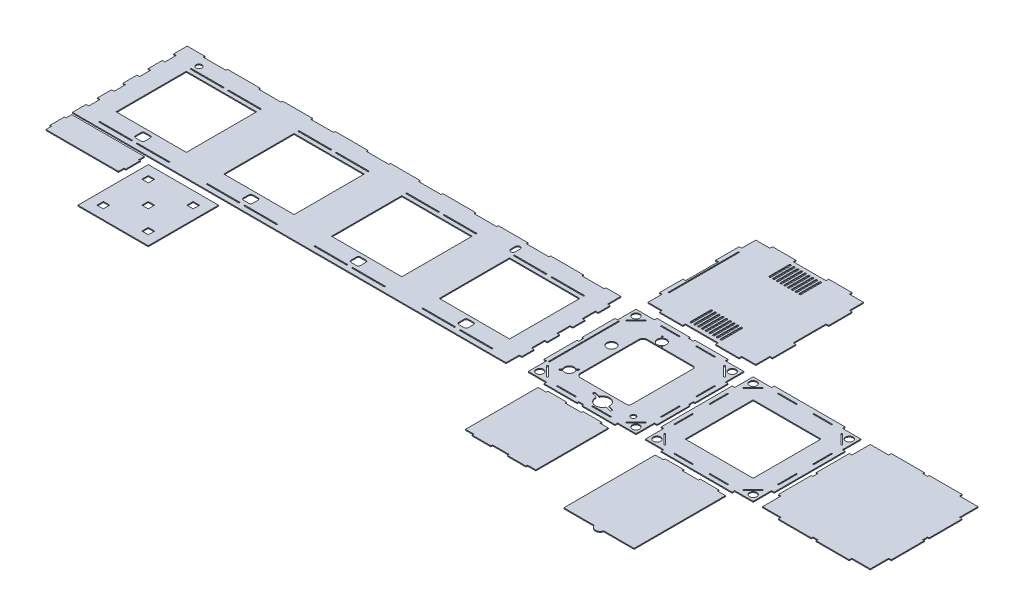
SolidWorks part; units mm, degrees
ref_plane "Front" through (0, 0, 0) normal (0, 0, 1) x (1, 0, 0)
ref_plane "Top" through (0, 0, 0) normal (0, 1, 0) x (1, 0, 0)
ref_plane "Right" through (0, 0, 0) normal (1, 0, 0) x (0, 0, -1)
sketch "Sketch1" plane through (0, 0, 0) normal (0, 1, 0) x (1, 0, 0)
  line L0 (0, 0) -> (438.15, 0) construction
  line L2 (-146.05, 155.575) -> (-146.05, -155.575) construction
  line L4 (146.05, 155.575) -> (146.05, -155.575) construction
  line L5 (-146.05, 155.575) -> (146.05, -155.575) construction
  line L6 (-146.05, -155.575) -> (146.05, 155.575) construction
  line L11 (146.05, 155.575) -> (438.15, 155.575)
  line L12 (146.05, 155.575) -> (146.05, -155.575) construction
  line L13 (146.05, -155.575) -> (438.15, -155.575)
  line L14 (438.15, 155.575) -> (438.15, -155.575) construction
  line L19 (-146.05, -155.575) -> (-438.15, -155.575)
  line L20 (-146.05, -155.575) -> (-146.05, 155.575) construction
  line L21 (-146.05, 155.575) -> (-438.15, 155.575)
  line L28 (146.05, -155.575) -> (-146.05, -155.575)
  line L34 (146.05, 155.575) -> (-146.05, 155.575)
  line L35 (-438.15, 155.575) -> (-438.15, -155.575) construction
  line L43 (-438.15, 155.575) -> (-730.25, 155.575)
  line L44 (-730.25, 155.575) -> (-730.25, -155.575) construction
  line L45 (-730.25, -155.575) -> (-438.15, -155.575)
  line L46 (438.15, 155.575) -> (438.15, 119.6594)
  line L47 (438.15, 119.6594) -> (445.262, 119.6594)
  line L48 (445.262, 119.6594) -> (445.262, 86.7664)
  line L49 (445.262, 86.7664) -> (438.15, 86.7664)
  line L50 (438.15, 86.7664) -> (438.15, 50.8508)
  line L51 (438.15, 50.8508) -> (445.262, 50.8508)
  line L63 (445.262, 50.8508) -> (445.262, 17.9578)
  line L64 (445.262, 17.9578) -> (438.15, 17.9578)
  line L65 (438.15, 17.9578) -> (438.15, -17.9578)
  line L66 (438.15, -17.9578) -> (445.262, -17.9578)
  line L67 (445.262, -17.9578) -> (445.262, -50.8508)
  line L68 (445.262, -50.8508) -> (438.15, -50.8508)
  line L69 (438.15, -50.8508) -> (438.15, -86.7664)
  line L70 (438.15, -86.7664) -> (445.262, -86.7664)
  line L71 (445.262, -86.7664) -> (445.262, -119.6594)
  line L72 (445.262, -119.6594) -> (438.15, -119.6594)
  line L73 (438.15, -119.6594) -> (438.15, -155.575)
  line L74 (-730.25, 155.575) -> (-737.362, 155.575)
  line L76 (-737.362, 118.4529) -> (-730.25, 118.4529)
  line L78 (-730.25, 87.9729) -> (-737.362, 87.9729)
  line L80 (-737.362, 49.6443) -> (-730.25, 49.6443)
  line L82 (-730.25, 19.1643) -> (-737.362, 19.1643)
  line L84 (-737.362, -19.1643) -> (-730.25, -19.1643)
  line L86 (-730.25, -49.6443) -> (-737.362, -49.6443)
  line L88 (-737.362, -87.9729) -> (-730.25, -87.9729)
  line L90 (-730.25, -118.4529) -> (-737.362, -118.4529)
  line L92 (-737.362, -155.575) -> (-730.25, -155.575)
  line L93 (445.262, 34.4043) -> (-730.25, 34.4043) construction
  line L94 (-730.25, 103.2129) -> (445.262, 103.2129) construction
  line L95 (-737.362, 155.575) -> (-737.362, 118.4529)
  line L96 (-737.362, 87.9729) -> (-737.362, 49.6443)
  line L97 (-730.25, 118.4529) -> (-730.25, 87.9729)
  line L98 (-730.25, 49.6443) -> (-730.25, 19.1643)
  line L99 (-730.25, -19.1643) -> (-730.25, -49.6443)
  line L100 (-730.25, -87.9729) -> (-730.25, -118.4529)
  line L101 (-730.25, -103.2129) -> (445.262, -103.2129) construction
  line L102 (-730.25, -34.4043) -> (445.262, -34.4043) construction
  line L103 (-737.362, 19.1643) -> (-737.362, -19.1643)
  line L104 (-737.362, -49.6443) -> (-737.362, -87.9729)
  line L105 (-737.362, -118.4529) -> (-737.362, -155.575)
  point P0 (0, 0)
  dimension "D1" = 292.1
  dimension "D2" = 311.15
  dimension "D3" = 7.112
  dimension "D4" = 32.893
  dimension "D5" = 30.48
extrude "Boss-Extrude1" add sketch "Sketch1" along normal blind 2.54
sketch "Sketch4" plane through (0, 2.54, 0) normal (0, 1, 0) x (1, 0, 0)
  line L0 (-438.15, 155.575) -> (-438.15, -155.575) construction
  line L1 (-438.15, 155.575) -> (-438.15, -155.575)
  line L2 (-146.05, 155.575) -> (-146.05, -155.575) construction
  line L3 (-146.05, 155.575) -> (-146.05, -155.575)
  line L4 (146.05, 155.575) -> (146.05, -155.575) construction
  line L5 (146.05, 155.575) -> (146.05, -155.575)
sketch "Sketch5" plane through (0, 2.54, 0) normal (0, 1, 0) x (1, 0, 0)
  line L0 (-730.25, -19.1643) -> (-730.25, 19.1643) construction
  line L1 (-438.15, 0) -> (-730.25, 0) construction
  line L2 (-438.15, 155.575) -> (-438.15, -155.575) construction
  line L3 (-438.15, 0) -> (-146.05, 0) construction
  line L4 (-146.05, 155.575) -> (-146.05, -155.575) construction
  line L5 (-146.05, 0) -> (146.05, 0) construction
  line L6 (146.05, 155.575) -> (146.05, -155.575) construction
  line L7 (146.05, 0) -> (438.15, 0) construction
  line L8 (438.15, -17.9578) -> (438.15, 17.9578) construction
  line L9 (-584.2, 0) -> (-584.2, -155.575) construction
  line L10 (-737.362, -155.575) -> (438.15, -155.575) construction
  line L11 (-292.1, 0) -> (-292.1, -155.575) construction
  line L12 (0, 0) -> (0, -155.575) construction
  line L13 (292.1, 0) -> (292.1, -155.575) construction
  line L14 (-488.95, -142.875) -> (-488.95, -155.575) construction
  line L15 (-679.45, -139.7508) -> (-488.95, -139.7508)
  line L16 (-679.45, -139.7508) -> (-679.45, -142.875)
  line L17 (-679.45, -142.875) -> (-488.95, -142.875)
  line L18 (-488.95, -139.7508) -> (-488.95, -142.875)
  line L19 (-679.45, -139.7508) -> (-488.95, -142.875) construction
  line L20 (-679.45, -142.875) -> (-488.95, -139.7508) construction
  line L21 (-387.35, -139.7508) -> (-196.85, -139.7508)
  line L22 (-387.35, -139.7508) -> (-387.35, -142.875)
  line L23 (-387.35, -142.875) -> (-196.85, -142.875)
  line L24 (-196.85, -139.7508) -> (-196.85, -142.875)
  line L25 (-387.35, -139.7508) -> (-196.85, -142.875) construction
  line L26 (-387.35, -142.875) -> (-196.85, -139.7508) construction
  line L27 (-95.25, -142.875) -> (95.25, -142.875)
  line L28 (-95.25, -142.875) -> (-95.25, -139.7508)
  line L29 (-95.25, -139.7508) -> (95.25, -139.7508)
  line L30 (95.25, -142.875) -> (95.25, -139.7508)
  line L31 (-95.25, -142.875) -> (95.25, -139.7508) construction
  line L32 (-95.25, -139.7508) -> (95.25, -142.875) construction
  line L33 (196.85, -142.875) -> (387.35, -142.875)
  line L34 (196.85, -142.875) -> (196.85, -139.7508)
  line L35 (196.85, -139.7508) -> (387.35, -139.7508)
  line L36 (387.35, -142.875) -> (387.35, -139.7508)
  line L37 (196.85, -142.875) -> (387.35, -139.7508) construction
  line L38 (196.85, -139.7508) -> (387.35, -142.875) construction
  line L39 (196.85, 139.7508) -> (387.35, 142.875) construction
  line L40 (196.85, 142.875) -> (387.35, 139.7508) construction
  line L41 (-95.25, 139.7508) -> (95.25, 142.875) construction
  line L42 (-95.25, 142.875) -> (95.25, 139.7508) construction
  line L43 (-387.35, 142.875) -> (-196.85, 139.7508) construction
  line L44 (-387.35, 139.7508) -> (-196.85, 142.875) construction
  line L45 (-679.45, 142.875) -> (-488.95, 139.7508) construction
  line L46 (-679.45, 139.7508) -> (-488.95, 142.875) construction
  line L47 (-584.2, 0) -> (-584.2, 106.9721) construction
  line L48 (387.35, 142.875) -> (387.35, 139.7508) construction
  line L49 (196.85, 139.7508) -> (387.35, 139.7508) construction
  line L50 (196.85, 142.875) -> (196.85, 139.7508) construction
  line L51 (196.85, 142.875) -> (387.35, 142.875) construction
  line L52 (95.25, 142.875) -> (95.25, 139.7508) construction
  line L53 (-95.25, 139.7508) -> (95.25, 139.7508) construction
  line L54 (-95.25, 142.875) -> (-95.25, 139.7508) construction
  line L55 (-95.25, 142.875) -> (95.25, 142.875) construction
  line L56 (-196.85, 139.7508) -> (-196.85, 142.875) construction
  line L57 (-387.35, 142.875) -> (-196.85, 142.875) construction
  line L58 (-387.35, 139.7508) -> (-387.35, 142.875) construction
  line L59 (-387.35, 139.7508) -> (-196.85, 139.7508) construction
  line L60 (-488.95, 139.7508) -> (-488.95, 142.875) construction
  line L61 (-679.45, 142.875) -> (-488.95, 142.875) construction
  line L62 (-679.45, 139.7508) -> (-679.45, 142.875) construction
  line L63 (-679.45, 139.7508) -> (-488.95, 139.7508) construction
  line L64 (-292.1, 0) -> (-292.1, 106.9721) construction
  line L65 (-679.45, 95.25) -> (-488.95, 95.25)
  line L66 (-679.45, 95.25) -> (-679.45, -95.25)
  line L67 (-679.45, -95.25) -> (-488.95, -95.25)
  line L68 (-488.95, 95.25) -> (-488.95, -95.25)
  line L69 (-679.45, 95.25) -> (-488.95, -95.25) construction
  line L70 (-679.45, -95.25) -> (-488.95, 95.25) construction
  line L71 (-387.35, 95.25) -> (-196.85, 95.25)
  line L72 (-387.35, 95.25) -> (-387.35, -95.25)
  line L73 (-387.35, -95.25) -> (-196.85, -95.25)
  line L74 (-196.85, 95.25) -> (-196.85, -95.25)
  line L75 (-387.35, 95.25) -> (-196.85, -95.25) construction
  line L76 (-387.35, -95.25) -> (-196.85, 95.25) construction
  line L77 (-95.25, 95.25) -> (95.25, 95.25)
  line L78 (-95.25, 95.25) -> (-95.25, -95.25)
  line L79 (-95.25, -95.25) -> (95.25, -95.25)
  line L80 (95.25, 95.25) -> (95.25, -95.25)
  line L81 (-95.25, 95.25) -> (95.25, -95.25) construction
  line L82 (-95.25, -95.25) -> (95.25, 95.25) construction
  line L83 (196.85, 95.25) -> (387.35, 95.25)
  line L84 (196.85, 95.25) -> (196.85, -95.25)
  line L85 (196.85, -95.25) -> (387.35, -95.25)
  line L86 (387.35, 95.25) -> (387.35, -95.25)
  line L87 (196.85, 95.25) -> (387.35, -95.25) construction
  line L88 (196.85, -95.25) -> (387.35, 95.25) construction
  line L89 (0, 0) -> (0, 106.9721) construction
  line L90 (292.1, 0) -> (292.1, 106.9721) construction
  line L91 (-387.35, -95.25) -> (-387.35, -139.7508) construction
  line L92 (-679.45, 108.5342) -> (-488.95, 108.5342)
  line L93 (-679.45, 108.5342) -> (-679.45, 105.41)
  line L94 (-679.45, 105.41) -> (-488.95, 105.41)
  line L95 (-488.95, 108.5342) -> (-488.95, 105.41)
  line L96 (-679.45, 108.5342) -> (-488.95, 105.41) construction
  line L97 (-679.45, 105.41) -> (-488.95, 108.5342) construction
  line L98 (-387.35, 108.5342) -> (-196.85, 108.5342)
  line L99 (-387.35, 108.5342) -> (-387.35, 105.41)
  line L100 (-387.35, 105.41) -> (-196.85, 105.41)
  line L101 (-196.85, 108.5342) -> (-196.85, 105.41)
  line L102 (-387.35, 108.5342) -> (-196.85, 105.41) construction
  line L103 (-387.35, 105.41) -> (-196.85, 108.5342) construction
  line L104 (-95.25, 108.5342) -> (95.25, 108.5342)
  line L105 (-95.25, 108.5342) -> (-95.25, 105.41)
  line L106 (-95.25, 105.41) -> (95.25, 105.41)
  line L107 (95.25, 108.5342) -> (95.25, 105.41)
  line L108 (-95.25, 108.5342) -> (95.25, 105.41) construction
  line L109 (-95.25, 105.41) -> (95.25, 108.5342) construction
  line L110 (196.85, 108.5342) -> (387.35, 108.5342)
  line L111 (196.85, 108.5342) -> (196.85, 105.41)
  line L112 (196.85, 105.41) -> (387.35, 105.41)
  line L113 (387.35, 108.5342) -> (387.35, 105.41)
  line L114 (196.85, 108.5342) -> (387.35, 105.41) construction
  line L115 (196.85, 105.41) -> (387.35, 108.5342) construction
  line L116 (-196.85, -95.25) -> (-196.85, -139.7508) construction
  line L117 (-196.85, -117.5004) -> (-387.35, -117.5004) construction
  line L118 (-7.62, -130.2258) -> (7.62, -130.2258)
  line L119 (-299.72, -104.775) -> (-284.48, -104.775)
  line L120 (-304.8, -109.855) -> (-304.8, -125.1458)
  line L121 (-299.72, -130.2258) -> (-284.48, -130.2258)
  line L122 (-279.4, -109.855) -> (-279.4, -125.1458)
  line L123 (-304.8, -104.775) -> (-279.4, -130.2258) construction
  line L124 (-304.8, -130.2258) -> (-279.4, -104.775) construction
  line L125 (-12.7, -109.855) -> (-12.7, -125.1458)
  line L126 (-7.62, -104.775) -> (7.62, -104.775)
  line L127 (12.7, -109.855) -> (12.7, -125.1458)
  line L128 (284.48, -130.2258) -> (299.72, -130.2258)
  line L129 (279.4, -109.855) -> (279.4, -125.1458)
  line L130 (284.48, -104.775) -> (299.72, -104.775)
  line L131 (304.8, -109.855) -> (304.8, -125.1458)
  line L132 (-596.9, -109.855) -> (-596.9, -125.1458)
  line L133 (-591.82, -104.775) -> (-576.58, -104.775)
  line L134 (-571.5, -109.855) -> (-571.5, -125.1458)
  line L135 (-591.82, -130.2258) -> (-576.58, -130.2258)
  line L136 (438.15, 155.575) -> (-737.362, 155.575) construction
  line L137 (184.15, 130.1242) -> (184.15, 117.4242) construction
  line L138 (190.5, 130.1242) -> (190.5, 117.4242)
  line L139 (177.8, 130.1242) -> (177.8, 117.4242)
  line L141 (-737.362, 155.575) -> (-737.362, 118.4529) construction
  line L142 (184.15, 123.7742) -> (-673.862, 123.7742) construction
  arc A0 (-284.48, -104.775) -> (-279.4, -109.855) centre (-284.48, -109.855) cw
  arc A1 (-279.4, -125.1458) -> (-284.48, -130.2258) centre (-284.48, -125.1458) cw
  arc A2 (-299.72, -130.2258) -> (-304.8, -125.1458) centre (-299.72, -125.1458) cw
  arc A3 (-304.8, -109.855) -> (-299.72, -104.775) centre (-299.72, -109.855) cw
  arc A4 (-7.62, -130.2258) -> (-12.7, -125.1458) centre (-7.62, -125.1458) cw
  arc A5 (-12.7, -109.855) -> (-7.62, -104.775) centre (-7.62, -109.855) cw
  arc A6 (7.62, -104.775) -> (12.7, -109.855) centre (7.62, -109.855) cw
  arc A7 (12.7, -125.1458) -> (7.62, -130.2258) centre (7.62, -125.1458) cw
  arc A8 (284.48, -130.2258) -> (279.4, -125.1458) centre (284.48, -125.1458) cw
  arc A9 (279.4, -109.855) -> (284.48, -104.775) centre (284.48, -109.855) cw
  arc A10 (299.72, -104.775) -> (304.8, -109.855) centre (299.72, -109.855) cw
  arc A11 (304.8, -125.1458) -> (299.72, -130.2258) centre (299.72, -125.1458) cw
  arc A12 (-596.9, -109.855) -> (-591.82, -104.775) centre (-591.82, -109.855) cw
  arc A13 (-591.82, -130.2258) -> (-596.9, -125.1458) centre (-591.82, -125.1458) cw
  arc A14 (-576.58, -104.775) -> (-571.5, -109.855) centre (-576.58, -109.855) cw
  arc A15 (-571.5, -125.1458) -> (-576.58, -130.2258) centre (-576.58, -125.1458) cw
  arc A16 (190.5, 130.1242) -> (177.8, 130.1242) centre (184.15, 130.1242) ccw
  arc A17 (177.8, 117.4242) -> (190.5, 117.4242) centre (184.15, 117.4242) ccw
  circle A18 centre (-673.862, 123.7742) radius 7.9375
  point P27 (-584.2, -141.3129)
  point P32 (-292.1, -141.3129)
  point P37 (0, -141.3129)
  point P42 (292.1, -141.3129)
  point P66 (292.1, 141.3129)
  point P67 (0, 141.3129)
  point P68 (-292.1, 141.3129)
  point P69 (-584.2, 141.3129)
  point P106 (-292.1, -117.5004)
  point P148 (0, -130.2258)
  point P161 (-584.2, -130.2258)
  point P165 (184.15, 123.7742)
  dimension "D5" = 10.16
  dimension "D7" = 9.525
  dimension "D9" = 5.08
  dimension "D14" = 25.4
  dimension "D16" = 2.54
  dimension "D17" = 15.875
  dimension "D18" = 63.5
  dimension "D1" = 12.7
  dimension "D2" = 3.1242
  dimension "D3" = 190.5
  dimension "D4" = 190.5
  dimension "D6" = 9.525
  dimension "D8" = 25.4
  dimension "D10" = 3
  dimension "D12" = 47.0408
  dimension "D13" = 12.7
  dimension "D15" = 38.1
  dimension "D11" = 2
extrude "Cut-Extrude2" cut sketch "Sketch5" against normal through all
sketch "Sketch6" plane through (0, 0, 0) normal (0, 1, 0) x (1, 0, 0)
  line L0 (0, 0) -> (635, 0) construction
  line L1 (635, 0) -> (635, 149.606) construction
  line L2 (488.95, 146.05) -> (781.05, 146.05) construction
  line L3 (488.95, 146.05) -> (488.95, -146.05) construction
  line L4 (488.95, -146.05) -> (781.05, -146.05) construction
  line L5 (781.05, 146.05) -> (781.05, -146.05) construction
  line L6 (488.95, 146.05) -> (781.05, -146.05) construction
  line L7 (488.95, -146.05) -> (781.05, 146.05) construction
  line L8 (635, 0) -> (784.606, 0) construction
  line L9 (635, 0) -> (635, -149.606) construction
  line L10 (488.95, 96.139) -> (488.95, 146.05)
  line L11 (538.861, 153.162) -> (731.139, 153.162)
  line L12 (538.861, 153.162) -> (538.861, 146.05)
  line L13 (538.861, 146.05) -> (731.139, 146.05) construction
  line L14 (731.139, 153.162) -> (731.139, 146.05)
  line L15 (538.861, 153.162) -> (731.139, 146.05) construction
  line L16 (538.861, 146.05) -> (731.139, 153.162) construction
  line L17 (788.162, -96.139) -> (781.05, -96.139)
  line L18 (788.162, -96.139) -> (788.162, 96.139)
  line L19 (788.162, 96.139) -> (781.05, 96.139)
  line L20 (781.05, -96.139) -> (781.05, 96.139) construction
  line L21 (788.162, -96.139) -> (781.05, 96.139) construction
  line L22 (788.162, 96.139) -> (781.05, -96.139) construction
  line L23 (538.861, -153.162) -> (731.139, -153.162)
  line L24 (538.861, -153.162) -> (538.861, -146.05)
  line L25 (538.861, -146.05) -> (731.139, -146.05) construction
  line L26 (731.139, -153.162) -> (731.139, -146.05)
  line L27 (538.861, -153.162) -> (731.139, -146.05) construction
  line L28 (538.861, -146.05) -> (731.139, -153.162) construction
  line L29 (481.838, 96.139) -> (488.95, 96.139)
  line L30 (481.838, 96.139) -> (481.838, -96.139)
  line L31 (481.838, -96.139) -> (488.95, -96.139)
  line L32 (488.95, 96.139) -> (488.95, -96.139) construction
  line L33 (481.838, 96.139) -> (488.95, -96.139) construction
  line L34 (481.838, -96.139) -> (488.95, 96.139) construction
  line L35 (488.95, 146.05) -> (538.861, 146.05)
  line L36 (731.139, 146.05) -> (781.05, 146.05)
  line L37 (781.05, 146.05) -> (781.05, 96.139)
  line L38 (781.05, -96.139) -> (781.05, -146.05)
  line L39 (781.05, -146.05) -> (731.139, -146.05)
  line L40 (538.861, -146.05) -> (488.95, -146.05)
  line L41 (488.95, -146.05) -> (488.95, -96.139)
  line L42 (799.338, 96.139) -> (799.338, -96.139)
  line L43 (799.338, 96.139) -> (806.45, 96.139)
  line L44 (806.45, 96.139) -> (806.45, 146.05)
  line L45 (806.45, 146.05) -> (856.361, 146.05)
  line L46 (856.361, 153.162) -> (856.361, 146.05)
  line L47 (856.361, 153.162) -> (1048.639, 153.162)
  line L48 (1048.639, 153.162) -> (1048.639, 146.05)
  line L49 (1048.639, 146.05) -> (1098.55, 146.05)
  line L50 (1098.55, 146.05) -> (1098.55, 96.139)
  line L51 (1105.662, 96.139) -> (1098.55, 96.139)
  line L52 (1105.662, -96.139) -> (1105.662, 96.139)
  line L53 (1105.662, -96.139) -> (1098.55, -96.139)
  line L54 (1098.55, -96.139) -> (1098.55, -146.05)
  line L55 (1098.55, -146.05) -> (1048.639, -146.05)
  line L56 (1048.639, -153.162) -> (1048.639, -146.05)
  line L57 (856.361, -153.162) -> (1048.639, -153.162)
  line L58 (856.361, -153.162) -> (856.361, -146.05)
  line L59 (856.361, -146.05) -> (806.45, -146.05)
  line L60 (806.45, -146.05) -> (806.45, -96.139)
  line L61 (799.338, -96.139) -> (806.45, -96.139)
  line L62 (806.45, 146.05) -> (1098.55, -146.05) construction
  line L63 (1116.838, 96.139) -> (1116.838, -96.139)
  line L64 (1116.838, 96.139) -> (1123.95, 96.139)
  line L65 (1123.95, 96.139) -> (1123.95, 146.05)
  line L66 (1123.95, 146.05) -> (1173.861, 146.05)
  line L67 (1173.861, 153.162) -> (1173.861, 146.05)
  line L68 (1173.861, 153.162) -> (1366.139, 153.162)
  line L69 (1366.139, 153.162) -> (1366.139, 146.05)
  line L70 (1366.139, 146.05) -> (1416.05, 146.05)
  line L71 (1416.05, 146.05) -> (1416.05, 96.139)
  line L72 (1423.162, 96.139) -> (1416.05, 96.139)
  line L73 (1423.162, -96.139) -> (1423.162, 96.139)
  line L74 (1423.162, -96.139) -> (1416.05, -96.139)
  line L75 (1416.05, -96.139) -> (1416.05, -146.05)
  line L76 (1416.05, -146.05) -> (1366.139, -146.05)
  line L77 (1366.139, -153.162) -> (1366.139, -146.05)
  line L78 (1173.861, -153.162) -> (1366.139, -153.162)
  line L79 (1173.861, -153.162) -> (1173.861, -146.05)
  line L80 (1173.861, -146.05) -> (1123.95, -146.05)
  line L81 (1123.95, -146.05) -> (1123.95, -96.139)
  line L82 (1116.838, -96.139) -> (1123.95, -96.139)
  line L83 (1270, 153.162) -> (1270, -153.162) construction
  line L84 (860.425, 92.075) -> (1044.575, 92.075)
  line L85 (860.425, 92.075) -> (860.425, -92.075)
  line L86 (860.425, -92.075) -> (1044.575, -92.075)
  line L87 (1044.575, 92.075) -> (1044.575, -92.075)
  line L88 (860.425, 92.075) -> (1044.575, -92.075) construction
  line L89 (860.425, -92.075) -> (1044.575, 92.075) construction
  point P22 (485.394, 0)
  point P67 (952.5, 0)
  dimension "D1" = 292.1
  dimension "D2" = 292.1
  dimension "D3" = 7.112
  dimension "D4" = 192.278
  dimension "D5" = 635
  dimension "D7" = 317.5
  dimension "D8" = 184.15
  dimension "D9" = 11.176
  dimension "D6" = 3
extrude "Boss-Extrude2" add sketch "Sketch6" along normal blind 2.54 separate body
sketch "Sketch7" plane through (0, 0, 0) normal (0, 1, 0) x (1, 0, 0)
  line L0 (-679.45, 105.41) -> (-679.45, -91.186) construction
  line L1 (-732.917, -161.925) -> (-536.321, -161.925)
  line L2 (-732.917, -161.925) -> (-732.917, -177.165)
  line L3 (-732.917, -231.775) -> (-536.321, -231.775)
  line L4 (-536.321, -161.925) -> (-536.321, -177.165)
  line L5 (-732.917, -161.925) -> (-536.321, -231.775) construction
  line L6 (-732.917, -231.775) -> (-536.321, -161.925) construction
  line L7 (-679.45, 95.25) -> (-679.45, -95.25) construction
  line L8 (-679.45, -91.186) -> (-679.45, -95.25) construction
  line L9 (488.95, -96.139) -> (488.95, -146.05) construction
  line L10 (488.95, -146.05) -> (538.861, -146.05) construction
  line L12 (-732.917, -177.165) -> (-737.362, -177.165)
  line L13 (502.6443, -105.415) -> (529.585, -132.3557) construction
  line L14 (502.6443, -105.415) -> (500.4351, -107.6241) construction
  line L15 (500.4351, -107.6241) -> (527.3759, -134.5649) construction
  line L16 (529.585, -132.3557) -> (527.3759, -134.5649) construction
  line L17 (502.6443, -105.415) -> (527.3759, -134.5649) construction
  line L18 (500.4351, -107.6241) -> (529.585, -132.3557) construction
  line L19 (-737.362, -177.165) -> (-737.362, -216.535)
  line L20 (-737.362, -216.535) -> (-732.917, -216.535)
  line L21 (488.95, -96.139) -> (538.861, -146.05) construction
  line L22 (515.0101, -119.9899) -> (513.9055, -121.0945) construction
  line L23 (-732.917, -216.535) -> (-732.917, -231.775)
  line L24 (-536.321, -177.165) -> (-531.876, -177.165)
  line L25 (-531.876, -177.165) -> (-531.876, -216.535)
  line L26 (-531.876, -216.535) -> (-536.321, -216.535)
  line L27 (-536.321, -216.535) -> (-536.321, -231.775)
  line L28 (-737.362, -155.575) -> (438.15, -155.575) construction
  line L29 (-737.362, -118.4529) -> (-737.362, -155.575) construction
  point P0 (-634.619, -196.85)
  point P14 (515.0101, -119.9899)
  dimension "D1" = 69.85
  dimension "D2" = 4.064
  dimension "D3" = 3.1242
  dimension "D4" = 39.37
  dimension "D5" = 38.1
  dimension "D6" = 4.445
  dimension "D7" = 6.35
extrude "Boss-Extrude3" add sketch "Sketch7" along normal blind 2.54 separate body
sketch "Sketch8" plane through (0, 2.54, 0) normal (0, 1, 0) x (1, 0, 0)
  line L0 (500.4351, -107.6241) -> (527.3759, -134.5649) construction
  line L1 (529.585, -132.3557) -> (527.3759, -134.5649) construction
  line L2 (502.6443, -105.415) -> (529.585, -132.3557) construction
  line L3 (502.6443, -105.415) -> (500.4351, -107.6241) construction
  line L4 (500.4351, -107.6241) -> (527.3759, -134.5649)
  line L5 (529.585, -132.3557) -> (527.3759, -134.5649)
  line L6 (502.6443, -105.415) -> (529.585, -132.3557)
  line L7 (502.6443, -105.415) -> (500.4351, -107.6241)
  line L8 (488.95, 146.05) -> (781.05, -146.05) construction
  line L9 (529.585, 132.3557) -> (502.6443, 105.415)
  line L10 (529.585, 132.3557) -> (527.3759, 134.5649)
  line L11 (527.3759, 134.5649) -> (500.4351, 107.6241)
  line L12 (502.6443, 105.415) -> (500.4351, 107.6241)
  line L13 (767.3557, 105.415) -> (740.415, 132.3557)
  line L14 (767.3557, 105.415) -> (769.5649, 107.6241)
  line L15 (769.5649, 107.6241) -> (742.6241, 134.5649)
  line L16 (740.415, 132.3557) -> (742.6241, 134.5649)
  line L17 (740.415, -132.3557) -> (767.3557, -105.415)
  line L18 (740.415, -132.3557) -> (742.6241, -134.5649)
  line L19 (742.6241, -134.5649) -> (769.5649, -107.6241)
  line L20 (767.3557, -105.415) -> (769.5649, -107.6241)
  line L21 (806.45, -96.139) -> (856.361, -146.05) construction
  line L22 (817.9351, -107.6241) -> (820.1443, -105.415)
  line L23 (820.1443, -105.415) -> (847.085, -132.3557)
  line L24 (847.085, -132.3557) -> (844.8759, -134.5649)
  line L25 (831.4055, -121.0945) -> (833.6146, -118.8854) construction
  line L26 (817.9351, -107.6241) -> (844.8759, -134.5649)
  line L27 (806.45, 146.05) -> (1098.55, -146.05) construction
  line L28 (820.1443, 105.415) -> (817.9351, 107.6241)
  line L29 (844.8759, 134.5649) -> (817.9351, 107.6241)
  line L30 (844.8759, 134.5649) -> (847.085, 132.3557)
  line L31 (847.085, 132.3557) -> (820.1443, 105.415)
  line L32 (1057.915, 132.3557) -> (1060.1241, 134.5649)
  line L33 (1087.0649, 107.6241) -> (1060.1241, 134.5649)
  line L34 (1087.0649, 107.6241) -> (1084.8557, 105.415)
  line L35 (1084.8557, 105.415) -> (1057.915, 132.3557)
  line L36 (1084.8557, -105.415) -> (1087.0649, -107.6241)
  line L37 (1060.1241, -134.5649) -> (1087.0649, -107.6241)
  line L38 (1060.1241, -134.5649) -> (1057.915, -132.3557)
  line L39 (1057.915, -132.3557) -> (1084.8557, -105.415)
  circle A0 centre (635, 0) radius 20.7898 construction
  circle A1 centre (635, 0) radius 20.7898 construction
  circle A2 centre (635, 0) radius 20.7898 construction
  circle A3 centre (635, 0) radius 20.7898 construction
  circle A4 centre (952.5, 0) radius 130.2137 construction
  circle A5 centre (822.1654, 130.3346) radius 10
  circle A9 centre (1082.8346, 130.3346) radius 10
  circle A10 centre (1082.8346, -130.3346) radius 10
  circle A11 centre (822.1654, -130.3346) radius 10
  circle A12 centre (504.6654, 130.3346) radius 10
  circle A13 centre (765.3346, 130.3346) radius 10
  circle A14 centre (765.3346, -130.3346) radius 10
  circle A15 centre (504.6654, -130.3346) radius 10
  point P28 (635, 0)
  point P58 (952.5, 0)
  point P67 (952.5, 0)
  point P76 (635, 0)
  dimension "D3" = 20
  dimension "D4" = 22.225
  dimension "D6" = 22.225
  dimension "D1" = 4
  dimension "D2" = 4
  dimension "D5" = 4
  dimension "D7" = 4
extrude "Cut-Extrude3" cut sketch "Sketch8" against normal through all
sketch "Sketch9" plane through (0, 0, 0) normal (0, 1, 0) x (1, 0, 0)
  line L0 (-737.362, -155.575) -> (438.15, -155.575) construction
  line L1 (-511.876, -175.575) -> (-321.376, -175.575)
  line L2 (-511.876, -175.575) -> (-511.876, -366.075)
  line L3 (-511.876, -366.075) -> (-321.376, -366.075)
  line L4 (-321.376, -175.575) -> (-321.376, -366.075)
  line L5 (-511.876, -175.575) -> (-321.376, -366.075) construction
  line L6 (-511.876, -366.075) -> (-321.376, -175.575) construction
  line L7 (-425.262, -262.189) -> (-407.99, -262.189)
  line L8 (-425.262, -262.189) -> (-425.262, -279.461)
  line L9 (-425.262, -279.461) -> (-407.99, -279.461)
  line L10 (-407.99, -262.189) -> (-407.99, -279.461)
  line L11 (-425.262, -262.189) -> (-407.99, -279.461) construction
  line L12 (-425.262, -279.461) -> (-407.99, -262.189) construction
  line L13 (-477.5247, -209.9263) -> (-355.7273, -209.9263) construction
  line L14 (-477.5247, -209.9263) -> (-477.5247, -331.7237) construction
  line L15 (-477.5247, -331.7237) -> (-355.7273, -331.7237) construction
  line L16 (-355.7273, -209.9263) -> (-355.7273, -331.7237) construction
  line L17 (-477.5247, -209.9263) -> (-355.7273, -331.7237) construction
  line L18 (-477.5247, -331.7237) -> (-355.7273, -209.9263) construction
  line L19 (-486.1607, -201.2903) -> (-468.8887, -201.2903)
  line L20 (-486.1607, -201.2903) -> (-486.1607, -218.5623)
  line L21 (-486.1607, -218.5623) -> (-468.8887, -218.5623)
  line L22 (-468.8887, -201.2903) -> (-468.8887, -218.5623)
  line L23 (-486.1607, -201.2903) -> (-468.8887, -218.5623) construction
  line L24 (-486.1607, -218.5623) -> (-468.8887, -201.2903) construction
  line L25 (-486.1607, -323.0877) -> (-468.8887, -323.0877)
  line L26 (-486.1607, -323.0877) -> (-486.1607, -340.3597)
  line L27 (-486.1607, -340.3597) -> (-468.8887, -340.3597)
  line L28 (-468.8887, -323.0877) -> (-468.8887, -340.3597)
  line L29 (-486.1607, -323.0877) -> (-468.8887, -340.3597) construction
  line L30 (-486.1607, -340.3597) -> (-468.8887, -323.0877) construction
  line L31 (-347.0913, -323.0877) -> (-364.3633, -323.0877)
  line L32 (-347.0913, -323.0877) -> (-347.0913, -340.3597)
  line L33 (-347.0913, -340.3597) -> (-364.3633, -340.3597)
  line L34 (-364.3633, -323.0877) -> (-364.3633, -340.3597)
  line L35 (-347.0913, -323.0877) -> (-364.3633, -340.3597) construction
  line L36 (-347.0913, -340.3597) -> (-364.3633, -323.0877) construction
  line L37 (-364.3633, -201.2903) -> (-347.0913, -201.2903)
  line L38 (-364.3633, -201.2903) -> (-364.3633, -218.5623)
  line L39 (-364.3633, -218.5623) -> (-347.0913, -218.5623)
  line L40 (-347.0913, -201.2903) -> (-347.0913, -218.5623)
  line L41 (-364.3633, -201.2903) -> (-347.0913, -218.5623) construction
  line L42 (-364.3633, -218.5623) -> (-347.0913, -201.2903) construction
  line L43 (-531.876, -216.535) -> (-531.876, -177.165) construction
  point P0 (-416.626, -270.825)
  point P5 (-416.626, -270.825)
  point P12 (-416.626, -270.825)
  dimension "D1" = 190.5
  dimension "D2" = 190.5
  dimension "D3" = 17.272
  dimension "D4" = 17.272
  dimension "D5" = 20
  dimension "D6" = 20
  dimension "D7" = 121.7975
extrude "Boss-Extrude4" add sketch "Sketch9" along normal blind 2.54 separate body
sketch "Sketch10" plane through (0, 2.54, 0) normal (0, 1, 0) x (1, 0, 0)
  line L0 (-488.95, 95.25) -> (-679.45, 95.25) construction
  line L1 (-196.85, 95.25) -> (-387.35, 95.25) construction
  line L2 (95.25, 95.25) -> (-95.25, 95.25) construction
  line L3 (387.35, 95.25) -> (196.85, 95.25) construction
  line L4 (-574.04, 95.25) -> (-594.36, 95.25)
  line L5 (-281.94, 95.25) -> (-302.26, 95.25)
  line L6 (10.16, 95.25) -> (-10.16, 95.25)
  line L7 (302.26, 95.25) -> (281.94, 95.25)
  line L8 (-679.45, -91.186) -> (-488.95, -91.186)
  line L9 (-584.2, -91.186) -> (-584.2, -95.25) construction
  line L14 (-679.45, 95.25) -> (-679.45, -95.25) construction
  line L15 (-488.95, -95.25) -> (-488.95, 95.25) construction
  line L16 (-679.45, -95.25) -> (-488.95, -95.25) construction
  line L17 (-387.35, -91.186) -> (-196.85, -91.186)
  line L18 (-387.35, 95.25) -> (-387.35, -95.25) construction
  line L19 (-196.85, -95.25) -> (-196.85, 95.25) construction
  line L20 (-95.25, -91.186) -> (95.25, -91.186)
  line L21 (-95.25, 95.25) -> (-95.25, -95.25) construction
  line L22 (95.25, -95.25) -> (95.25, 95.25) construction
  line L23 (196.85, -91.186) -> (387.35, -91.186)
  line L24 (196.85, 95.25) -> (196.85, -95.25) construction
  line L25 (387.35, -95.25) -> (387.35, 95.25) construction
  arc A0 (-594.36, 95.25) -> (-574.04, 95.25) centre (-584.2, 95.25) ccw
  arc A1 (-302.26, 95.25) -> (-281.94, 95.25) centre (-292.1, 95.25) ccw
  arc A2 (-10.16, 95.25) -> (10.16, 95.25) centre (0, 95.25) ccw
  arc A3 (281.94, 95.25) -> (302.26, 95.25) centre (292.1, 95.25) ccw
  dimension "D1" = 20.32
  dimension "D2" = 4.064
sketch "Sketch11" plane through (0, 2.54, 0) normal (0, 1, 0) x (1, 0, 0)
  line L0 (488.95, 146.05) -> (781.05, -146.05) construction
  line L18 (731.139, -146.05) -> (781.05, -146.05) construction
  line L19 (781.05, -146.05) -> (781.05, -96.139) construction
  line L109 (679.0012, -124.5383) -> (690.5024, -127.62)
  line L110 (692.0801, -121.7317) -> (680.579, -118.65)
  line L111 (642.245, -108.3784) -> (630.7438, -105.2967)
  line L112 (629.1661, -111.185) -> (640.6672, -114.2667)
  line L126 (551.6771, -78.5338) -> (554.4254, -75.7854)
  line L127 (550.8333, -72.1933) -> (548.085, -74.9417)
  line L128 (529.0957, -93.9309) -> (526.3474, -96.6793)
  line L129 (529.9395, -100.2714) -> (532.6878, -97.523)
  line L130 (699.863, 90.3227) -> (574.863, 90.3227)
  line L131 (563.5613, 79.021) -> (563.5613, -78.979)
  line L132 (574.863, -90.2808) -> (699.863, -90.2808)
  line L137 (706.1648, -83.979) -> (706.1648, 84.021)
  circle A0 centre (540.385, 28.067) radius 12.6875
  circle A1 centre (600.5844, 104.3237) radius 12.6875
  circle A2 centre (612.3808, 93.3292) radius 1.7055
  circle A3 centre (588.3905, 117.3172) radius 1.7055
  arc A4 (673.6061, -130.382) -> (677.5437, -125.183) centre (660.6231, -116.4583) ccw
  arc A5 (679.6391, -117.3629) -> (643.7025, -107.7337) centre (660.6231, -116.4583) ccw
  arc A6 (641.6071, -115.5538) -> (673.6061, -130.382) centre (660.6231, -116.4583) ccw
  arc A7 (706.1648, 84.021) -> (699.863, 90.3227) centre (699.863, 84.021) ccw
  arc A8 (699.863, -90.2808) -> (706.1648, -83.979) centre (699.863, -83.979) ccw
  arc A9 (563.5613, -78.979) -> (574.863, -90.2808) centre (574.863, -78.979) ccw
  arc A10 (574.863, 90.3227) -> (563.5613, 79.021) centre (574.863, 79.021) ccw
  circle A14 centre (540.385, 28.067) radius 12.6875 construction
  circle A15 centre (600.5844, 104.3237) radius 12.6875 construction
  circle A16 centre (612.3808, 93.3292) radius 1.7055 construction
  circle A17 centre (588.3905, 117.3172) radius 1.7055 construction
  circle A24 centre (737.0572, -109.22) radius 6.7474
  arc A97 (673.6061, -130.382) -> (677.5437, -125.183) centre (660.6231, -116.4583) ccw construction
  arc A98 (679.0012, -124.5383) -> (677.5437, -125.183) centre (678.6725, -125.765) ccw
  arc A99 (690.5024, -127.62) -> (692.0801, -121.7317) centre (691.2913, -124.6758) ccw
  arc A100 (679.6391, -117.3629) -> (680.579, -118.65) centre (680.9077, -117.4233) ccw
  arc A101 (679.6391, -117.3629) -> (643.7025, -107.7337) centre (660.6231, -116.4583) ccw construction
  arc A102 (642.245, -108.3784) -> (643.7025, -107.7337) centre (642.5737, -107.1517) ccw
  arc A103 (630.7438, -105.2967) -> (629.1661, -111.185) centre (629.955, -108.2408) ccw
  arc A104 (641.6071, -115.5538) -> (640.6672, -114.2667) centre (640.3385, -115.4934) ccw
  arc A105 (641.6071, -115.5538) -> (673.6061, -130.382) centre (660.6231, -116.4583) ccw construction
  arc A120 (551.6771, -78.5338) -> (551.466, -80.0506) centre (552.5751, -79.4318) ccw
  arc A121 (554.4254, -75.7854) -> (550.8333, -72.1933) centre (552.6294, -73.9893) ccw
  arc A122 (546.5682, -75.1527) -> (548.085, -74.9417) centre (547.1869, -74.0436) ccw
  arc A123 (546.5682, -75.1527) -> (529.3068, -92.4141) centre (540.3864, -86.2323) ccw
  arc A124 (529.0957, -93.9309) -> (529.3068, -92.4141) centre (528.1977, -93.0329) ccw
  arc A125 (526.3474, -96.6793) -> (529.9395, -100.2714) centre (528.1434, -98.4753) ccw
  arc A126 (534.2046, -97.312) -> (532.6878, -97.523) centre (533.5858, -98.421) ccw
  arc A127 (534.2046, -97.312) -> (551.466, -80.0506) centre (540.3864, -86.2323) ccw
  arc A128 (706.1648, 84.021) -> (699.863, 90.3227) centre (699.863, 84.021) ccw construction
  arc A129 (574.863, 90.3227) -> (563.5613, 79.021) centre (574.863, 79.021) ccw construction
  arc A130 (563.5613, -78.979) -> (574.863, -90.2808) centre (574.863, -78.979) ccw construction
  arc A166 (699.863, -90.2808) -> (706.1648, -83.979) centre (699.863, -83.979) ccw construction
  dimension "D1" = 13.4948
  dimension "D2" = 36.83
  dimension "D3" = 43.9928
  dimension "D4" = 6.5219
extrude "Cut-Extrude4" cut sketch "Sketch11" against normal through all
sketch "Sketch12" plane through (0, 2.54, 0) normal (0, 1, 0) x (1, 0, 0)
  line L0 (481.838, 0) -> (563.5613, 0.021) construction
  line L1 (481.838, 96.139) -> (481.838, -96.139) construction
  line L2 (563.5613, 79.021) -> (563.5613, -78.979) construction
  line L3 (494.0935, 95.2531) -> (494.0935, 0.0031) construction
  line L4 (492.633, 95.2531) -> (495.554, 95.2531) construction
  line L5 (492.633, 95.2531) -> (492.633, -95.2469) construction
  line L6 (492.633, -95.2469) -> (495.554, -95.2469) construction
  line L7 (495.554, 95.2531) -> (495.554, -95.2469) construction
  line L8 (492.633, 95.2531) -> (495.554, -95.2469) construction
  line L9 (492.633, -95.2469) -> (495.554, 95.2531) construction
  line L10 (494.0935, 0.0031) -> (494.0935, -95.2469) construction
  line L11 (488.95, 146.05) -> (781.05, -146.05) construction
  line L12 (492.633, -22.2219) -> (495.554, -22.2219)
  line L13 (492.633, -22.2219) -> (492.633, -73.0219)
  line L14 (492.633, -73.0219) -> (495.554, -73.0219)
  line L15 (495.554, -22.2219) -> (495.554, -73.0219)
  line L16 (492.633, -22.2219) -> (495.554, -73.0219) construction
  line L17 (492.633, -73.0219) -> (495.554, -22.2219) construction
  line L18 (492.633, 73.0281) -> (495.554, 73.0281)
  line L19 (492.633, 73.0281) -> (492.633, 22.2281)
  line L20 (492.633, 22.2281) -> (495.554, 22.2281)
  line L21 (495.554, 73.0281) -> (495.554, 22.2281)
  line L22 (492.633, 73.0281) -> (495.554, 22.2281) construction
  line L23 (492.633, 22.2281) -> (495.554, 73.0281) construction
  line L24 (708.0281, 142.367) -> (657.2281, 142.367)
  line L25 (612.7781, 142.367) -> (612.7781, 139.446)
  line L26 (612.7781, 142.367) -> (561.9781, 142.367)
  line L27 (612.7781, 139.446) -> (561.9781, 139.446)
  line L28 (708.0281, 139.446) -> (657.2281, 139.446)
  line L29 (657.2281, 142.367) -> (657.2281, 139.446)
  line L30 (708.0281, 142.367) -> (708.0281, 139.446)
  line L31 (561.9781, 142.367) -> (561.9781, 139.446)
  line L32 (777.367, -73.0281) -> (777.367, -22.2281)
  line L33 (777.367, 22.2219) -> (774.446, 22.2219)
  line L34 (777.367, 22.2219) -> (777.367, 73.0219)
  line L35 (774.446, 22.2219) -> (774.446, 73.0219)
  line L36 (774.446, -73.0281) -> (774.446, -22.2281)
  line L37 (777.367, -22.2281) -> (774.446, -22.2281)
  line L38 (777.367, -73.0281) -> (774.446, -73.0281)
  line L39 (777.367, 73.0219) -> (774.446, 73.0219)
  line L40 (561.9719, -142.367) -> (612.7719, -142.367)
  line L41 (657.2219, -142.367) -> (657.2219, -139.446)
  line L42 (657.2219, -142.367) -> (708.0219, -142.367)
  line L43 (657.2219, -139.446) -> (708.0219, -139.446)
  line L44 (561.9719, -139.446) -> (612.7719, -139.446)
  line L45 (612.7719, -142.367) -> (612.7719, -139.446)
  line L46 (561.9719, -142.367) -> (561.9719, -139.446)
  line L47 (708.0219, -142.367) -> (708.0219, -139.446)
  line L48 (799.338, 0) -> (860.425, 0) construction
  line L49 (799.338, 96.139) -> (799.338, -96.139) construction
  line L50 (860.425, 92.075) -> (860.425, -92.075) construction
  line L51 (495.554, 73.0281) -> (810.133, 73.0281) construction
  line L52 (495.554, -22.2219) -> (810.133, -22.2219) construction
  line L53 (810.133, 73.0281) -> (810.133, -22.2219) construction
  line L54 (492.633, 22.2281) -> (481.838, 22.2281) construction
  line L55 (810.133, 73.0281) -> (813.054, 73.0281)
  line L56 (810.133, 73.0281) -> (810.133, 22.2281)
  line L57 (810.133, 22.2281) -> (813.054, 22.2281)
  line L58 (813.054, 73.0281) -> (813.054, 22.2281)
  line L59 (810.133, -22.2219) -> (813.054, -22.2219)
  line L60 (810.133, -22.2219) -> (810.133, -73.0219)
  line L61 (810.133, -73.0219) -> (813.054, -73.0219)
  line L62 (813.054, -22.2219) -> (813.054, -73.0219)
  line L63 (810.133, 22.2281) -> (799.338, 22.2281) construction
  line L64 (806.45, 146.05) -> (1098.55, -146.05) construction
  line L65 (1025.5281, 142.367) -> (974.7281, 142.367)
  line L66 (1025.5281, 142.367) -> (1025.5281, 139.446)
  line L67 (1025.5281, 139.446) -> (974.7281, 139.446)
  line L68 (974.7281, 142.367) -> (974.7281, 139.446)
  line L69 (930.2781, 139.446) -> (879.4781, 139.446)
  line L70 (930.2781, 142.367) -> (930.2781, 139.446)
  line L71 (930.2781, 142.367) -> (879.4781, 142.367)
  line L72 (879.4781, 142.367) -> (879.4781, 139.446)
  line L73 (1094.867, -73.0281) -> (1094.867, -22.2281)
  line L74 (1094.867, -73.0281) -> (1091.946, -73.0281)
  line L75 (1091.946, -73.0281) -> (1091.946, -22.2281)
  line L76 (1094.867, -22.2281) -> (1091.946, -22.2281)
  line L77 (1091.946, 22.2219) -> (1091.946, 73.0219)
  line L78 (1094.867, 22.2219) -> (1091.946, 22.2219)
  line L79 (1094.867, 22.2219) -> (1094.867, 73.0219)
  line L80 (1094.867, 73.0219) -> (1091.946, 73.0219)
  line L81 (879.4719, -142.367) -> (930.2719, -142.367)
  line L82 (879.4719, -142.367) -> (879.4719, -139.446)
  line L83 (879.4719, -139.446) -> (930.2719, -139.446)
  line L84 (930.2719, -142.367) -> (930.2719, -139.446)
  line L85 (974.7219, -139.446) -> (1025.5219, -139.446)
  line L86 (974.7219, -142.367) -> (974.7219, -139.446)
  line L87 (974.7219, -142.367) -> (1025.5219, -142.367)
  line L88 (1025.5219, -142.367) -> (1025.5219, -139.446)
  point P6 (494.0935, 0.0031)
  point P13 (494.0935, -47.6219)
  point P19 (635, 0)
  point P21 (494.0935, 47.6281)
  point P55 (635, 0)
  point P74 (952.5, 0)
  point P102 (952.5, 0)
  dimension "D1" = 2.921
  dimension "D2" = 190.5
  dimension "D3" = 10.795
  dimension "D4" = 50.8
  dimension "D5" = 4
  dimension "D6" = 4
extrude "Cut-Extrude5" cut sketch "Sketch12" against normal through all
sketch "Sketch13" plane through (0, 2.54, 0) normal (0, 1, 0) x (1, 0, 0)
  line L0 (492.633, 22.2281) -> (495.554, -22.2219) construction
  line L1 (495.554, -73.0219) -> (495.554, -22.2219) construction
  line L2 (492.633, 95.2531) -> (495.554, 95.2531)
  line L3 (492.633, 95.2531) -> (492.633, -95.2469)
  line L4 (492.633, -95.2469) -> (495.554, -95.2469)
  line L5 (495.554, 95.2531) -> (495.554, -95.2469)
  line L6 (492.633, 95.2531) -> (495.554, -95.2469) construction
  line L7 (492.633, -95.2469) -> (495.554, 95.2531) construction
  point P4 (494.0935, 0.0031)
  dimension "D1" = 190.5
extrude "Cut-Extrude6" cut sketch "Sketch13" against normal through all
sketch "Sketch14" plane through (0, 0, 0) normal (0, 1, 0) x (1, 0, 0)
  line L0 (-732.917, -231.775) -> (-536.321, -231.775) construction
  line L1 (539.7469, -170.307) -> (561.9719, -170.307)
  line L2 (539.7469, -170.307) -> (539.7469, -366.903)
  line L3 (539.7469, -366.903) -> (561.9719, -366.903)
  line L4 (730.2469, -170.307) -> (730.2469, -366.903)
  line L5 (539.7469, -170.307) -> (730.2469, -366.903) construction
  line L6 (539.7469, -366.903) -> (730.2469, -170.307) construction
  line L9 (561.9719, -142.367) -> (612.7719, -142.367) construction
  line L10 (612.7719, -142.367) -> (657.2219, -142.367) construction
  line L11 (657.2219, -142.367) -> (708.0219, -142.367) construction
  line L12 (538.861, -153.162) -> (731.139, -153.162) construction
  line L13 (635, 324.612) -> (635, 153.162) construction
  line L14 (561.9719, -142.367) -> (561.9719, -170.307) construction
  line L15 (612.7719, -142.367) -> (612.7719, -170.307) construction
  line L16 (657.2219, -142.367) -> (657.2219, -170.307) construction
  line L17 (708.0219, -142.367) -> (708.0219, -170.307) construction
  line L18 (634.9969, -268.605) -> (730.2469, -268.605) construction
  line L19 (561.9719, -170.307) -> (561.9719, -165.862)
  line L20 (561.9719, -165.862) -> (612.7719, -165.862)
  line L21 (612.7719, -165.862) -> (612.7719, -170.307)
  line L22 (657.2219, -170.307) -> (657.2219, -165.862)
  line L23 (657.2219, -165.862) -> (708.0219, -165.862)
  line L24 (708.0219, -165.862) -> (708.0219, -170.307)
  line L25 (612.7719, -170.307) -> (657.2219, -170.307)
  line L26 (708.0219, -170.307) -> (730.2469, -170.307)
  line L27 (708.0219, -371.348) -> (708.0219, -366.903)
  line L28 (657.2219, -371.348) -> (708.0219, -371.348)
  line L29 (657.2219, -366.903) -> (657.2219, -371.348)
  line L30 (612.7719, -371.348) -> (612.7719, -366.903)
  line L31 (561.9719, -366.903) -> (561.9719, -371.348)
  line L32 (561.9719, -371.348) -> (612.7719, -371.348)
  line L33 (612.7719, -366.903) -> (657.2219, -366.903)
  line L34 (708.0219, -366.903) -> (730.2469, -366.903)
  line L35 (952.5, -153.162) -> (952.5, -294.132) construction
  line L36 (488.95, 470.662) -> (527.05, 470.662)
  line L37 (857.25, -170.307) -> (879.4719, -170.307)
  line L38 (857.25, -170.307) -> (857.25, -417.957)
  line L39 (857.25, -417.957) -> (939.8, -417.957)
  line L40 (1047.75, -170.307) -> (1047.75, -417.957)
  line L41 (857.25, -170.307) -> (1047.75, -417.957) construction
  line L42 (857.25, -417.957) -> (1047.75, -170.307) construction
  line L43 (856.361, -153.162) -> (1048.639, -153.162) construction
  line L44 (879.4719, -142.367) -> (879.4719, -170.307) construction
  line L45 (930.2719, -142.367) -> (930.2719, -170.307) construction
  line L46 (974.7219, -142.367) -> (974.7219, -170.307) construction
  line L47 (1025.5219, -142.367) -> (1025.5219, -170.307) construction
  line L48 (879.4719, -170.307) -> (879.4719, -165.862)
  line L49 (879.4719, -165.862) -> (930.2719, -165.862)
  line L50 (930.2719, -165.862) -> (930.2719, -170.307)
  line L51 (974.7219, -170.307) -> (974.7219, -165.862)
  line L52 (974.7219, -165.862) -> (1025.5219, -165.862)
  line L53 (1025.5219, -165.862) -> (1025.5219, -170.307)
  line L54 (930.2719, -170.307) -> (974.7219, -170.307)
  line L55 (1025.5219, -170.307) -> (1047.75, -170.307)
  line L56 (952.5, -294.132) -> (952.5, -414.666) construction
  line L57 (965.2, -417.957) -> (1047.75, -417.957)
  line L58 (488.95, 470.662) -> (488.95, 432.562)
  line L59 (488.95, 178.562) -> (527.05, 178.562)
  line L60 (781.05, 470.662) -> (781.05, 432.562)
  line L61 (488.95, 470.662) -> (781.05, 178.562) construction
  line L62 (488.95, 178.562) -> (781.05, 470.662) construction
  line L63 (731.139, 153.162) -> (538.861, 153.162) construction
  line L64 (488.95, 146.05) -> (488.95, -146.05) construction
  line L65 (635, 324.612) -> (781.05, 324.612) construction
  line L66 (635, 244.9068) -> (635, 190.9318) construction
  line L69 (635, 324.612) -> (635, 401.7772) construction
  line L70 (632.46, 244.9068) -> (632.46, 190.9318)
  line L75 (635, 404.3172) -> (635, 458.2922) construction
  line L76 (632.46, 404.3172) -> (632.46, 458.2922)
  line L77 (637.54, 404.3172) -> (637.54, 458.2922)
  line L78 (637.54, 244.9068) -> (637.54, 190.9318)
  line L79 (645.16, 404.3172) -> (645.16, 458.2922) construction
  line L80 (642.62, 404.3172) -> (642.62, 458.2922)
  line L81 (647.7, 404.3172) -> (647.7, 458.2922)
  line L82 (645.16, 244.9068) -> (645.16, 190.9318) construction
  line L83 (642.62, 244.9068) -> (642.62, 190.9318)
  line L84 (647.7, 244.9068) -> (647.7, 190.9318)
  line L85 (655.32, 404.3172) -> (655.32, 458.2922) construction
  line L86 (652.78, 404.3172) -> (652.78, 458.2922)
  line L87 (657.86, 404.3172) -> (657.86, 458.2922)
  line L88 (655.32, 244.9068) -> (655.32, 190.9318) construction
  line L89 (652.78, 244.9068) -> (652.78, 190.9318)
  line L90 (657.86, 244.9068) -> (657.86, 190.9318)
  line L91 (665.48, 404.3172) -> (665.48, 458.2922) construction
  line L92 (662.94, 404.3172) -> (662.94, 458.2922)
  line L93 (668.02, 404.3172) -> (668.02, 458.2922)
  line L94 (665.48, 244.9068) -> (665.48, 190.9318) construction
  line L95 (662.94, 244.9068) -> (662.94, 190.9318)
  line L96 (668.02, 244.9068) -> (668.02, 190.9318)
  line L97 (675.64, 404.3172) -> (675.64, 458.2922) construction
  line L98 (673.1, 404.3172) -> (673.1, 458.2922)
  line L99 (678.18, 404.3172) -> (678.18, 458.2922)
  line L100 (675.64, 244.9068) -> (675.64, 190.9318) construction
  line L101 (673.1, 244.9068) -> (673.1, 190.9318)
  line L102 (678.18, 244.9068) -> (678.18, 190.9318)
  line L103 (624.84, 404.3172) -> (624.84, 458.2922) construction
  line L104 (622.3, 404.3172) -> (622.3, 458.2922)
  line L105 (627.38, 404.3172) -> (627.38, 458.2922)
  line L106 (624.84, 244.9068) -> (624.84, 190.9318) construction
  line L107 (622.3, 244.9068) -> (622.3, 190.9318)
  line L108 (627.38, 244.9068) -> (627.38, 190.9318)
  line L109 (614.68, 404.3172) -> (614.68, 458.2922) construction
  line L110 (612.14, 404.3172) -> (612.14, 458.2922)
  line L111 (617.22, 404.3172) -> (617.22, 458.2922)
  line L112 (614.68, 244.9068) -> (614.68, 190.9318) construction
  line L113 (612.14, 244.9068) -> (612.14, 190.9318)
  line L114 (617.22, 244.9068) -> (617.22, 190.9318)
  line L115 (604.52, 404.3172) -> (604.52, 458.2922) construction
  line L116 (601.98, 404.3172) -> (601.98, 458.2922)
  line L117 (607.06, 404.3172) -> (607.06, 458.2922)
  line L118 (604.52, 244.9068) -> (604.52, 190.9318) construction
  line L119 (601.98, 244.9068) -> (601.98, 190.9318)
  line L120 (607.06, 244.9068) -> (607.06, 190.9318)
  line L121 (594.36, 404.3172) -> (594.36, 458.2922) construction
  line L122 (591.82, 404.3172) -> (591.82, 458.2922)
  line L123 (596.9, 404.3172) -> (596.9, 458.2922)
  line L124 (594.36, 244.9068) -> (594.36, 190.9318) construction
  line L125 (591.82, 244.9068) -> (591.82, 190.9318)
  line L126 (596.9, 244.9068) -> (596.9, 190.9318)
  line L127 (635, 324.612) -> (488.95, 324.612) construction
  line L128 (492.633, 95.2531) -> (492.633, -95.2469) construction
  line L129 (492.633, 419.862) -> (495.554, 419.862)
  line L130 (492.633, 419.862) -> (492.633, 229.362)
  line L131 (492.633, 229.362) -> (495.554, 229.362)
  line L132 (495.554, 419.862) -> (495.554, 229.362)
  line L133 (492.633, 419.862) -> (495.554, 229.362) construction
  line L134 (492.633, 229.362) -> (495.554, 419.862) construction
  line L135 (495.554, 95.2531) -> (492.633, 95.2531) construction
  line L136 (488.95, 369.062) -> (481.838, 369.062)
  line L137 (481.838, 369.062) -> (481.838, 432.562)
  line L138 (481.838, 432.562) -> (488.95, 432.562)
  line L139 (488.95, 216.662) -> (481.838, 216.662)
  line L140 (481.838, 216.662) -> (481.838, 280.162)
  line L141 (481.838, 280.162) -> (488.95, 280.162)
  line L142 (481.838, 432.562) -> (481.838, 216.662) construction
  line L143 (481.838, 324.612) -> (488.95, 324.612) construction
  line L144 (488.95, 369.062) -> (488.95, 280.162)
  line L145 (488.95, 216.662) -> (488.95, 178.562)
  line L146 (781.05, 216.662) -> (788.162, 216.662)
  line L147 (788.162, 216.662) -> (788.162, 280.162)
  line L148 (788.162, 280.162) -> (781.05, 280.162)
  line L149 (781.05, 369.062) -> (788.162, 369.062)
  line L150 (788.162, 369.062) -> (788.162, 432.562)
  line L151 (788.162, 432.562) -> (781.05, 432.562)
  line L152 (781.05, 369.062) -> (781.05, 280.162)
  line L153 (781.05, 216.662) -> (781.05, 178.562)
  line L154 (635, 469.9) -> (635, 477.774) construction
  line L155 (590.55, 477.774) -> (679.45, 477.774) construction
  line L156 (590.55, 470.662) -> (679.45, 470.662)
  line L158 (527.05, 470.662) -> (527.05, 477.774)
  line L159 (527.05, 477.774) -> (590.55, 477.774)
  line L160 (590.55, 470.662) -> (590.55, 477.774)
  line L161 (679.45, 477.774) -> (742.95, 477.774)
  line L162 (679.45, 477.774) -> (679.45, 470.662)
  line L164 (742.95, 477.774) -> (742.95, 470.662)
  line L165 (742.95, 470.662) -> (781.05, 470.662)
  line L166 (742.95, 171.45) -> (742.95, 178.562)
  line L167 (679.45, 171.45) -> (742.95, 171.45)
  line L168 (679.45, 171.45) -> (679.45, 178.562)
  line L169 (590.55, 178.562) -> (590.55, 171.45)
  line L170 (527.05, 171.45) -> (590.55, 171.45)
  line L171 (527.05, 178.562) -> (527.05, 171.45)
  line L172 (590.55, 178.562) -> (679.45, 178.562)
  line L173 (742.95, 178.562) -> (781.05, 178.562)
  arc A0 (939.8, -417.957) -> (965.2, -417.957) centre (952.5, -414.666) ccw
  arc A7 (632.46, 404.3172) -> (637.54, 404.3172) centre (635, 404.3172) ccw
  arc A8 (637.54, 458.2922) -> (632.46, 458.2922) centre (635, 458.2922) ccw
  arc A9 (632.46, 244.9068) -> (637.54, 244.9068) centre (635, 244.9068) cw
  arc A10 (637.54, 190.9318) -> (632.46, 190.9318) centre (635, 190.9318) cw
  arc A11 (642.62, 404.3172) -> (647.7, 404.3172) centre (645.16, 404.3172) ccw
  arc A12 (647.7, 458.2922) -> (642.62, 458.2922) centre (645.16, 458.2922) ccw
  arc A13 (642.62, 244.9068) -> (647.7, 244.9068) centre (645.16, 244.9068) cw
  arc A14 (647.7, 190.9318) -> (642.62, 190.9318) centre (645.16, 190.9318) cw
  arc A15 (652.78, 404.3172) -> (657.86, 404.3172) centre (655.32, 404.3172) ccw
  arc A16 (657.86, 458.2922) -> (652.78, 458.2922) centre (655.32, 458.2922) ccw
  arc A17 (652.78, 244.9068) -> (657.86, 244.9068) centre (655.32, 244.9068) cw
  arc A18 (657.86, 190.9318) -> (652.78, 190.9318) centre (655.32, 190.9318) cw
  arc A19 (662.94, 404.3172) -> (668.02, 404.3172) centre (665.48, 404.3172) ccw
  arc A20 (668.02, 458.2922) -> (662.94, 458.2922) centre (665.48, 458.2922) ccw
  arc A21 (662.94, 244.9068) -> (668.02, 244.9068) centre (665.48, 244.9068) cw
  arc A22 (668.02, 190.9318) -> (662.94, 190.9318) centre (665.48, 190.9318) cw
  arc A23 (673.1, 404.3172) -> (678.18, 404.3172) centre (675.64, 404.3172) ccw
  arc A24 (678.18, 458.2922) -> (673.1, 458.2922) centre (675.64, 458.2922) ccw
  arc A25 (673.1, 244.9068) -> (678.18, 244.9068) centre (675.64, 244.9068) cw
  arc A26 (678.18, 190.9318) -> (673.1, 190.9318) centre (675.64, 190.9318) cw
  arc A27 (622.3, 404.3172) -> (627.38, 404.3172) centre (624.84, 404.3172) ccw
  arc A28 (627.38, 458.2922) -> (622.3, 458.2922) centre (624.84, 458.2922) ccw
  arc A29 (622.3, 244.9068) -> (627.38, 244.9068) centre (624.84, 244.9068) cw
  arc A30 (627.38, 190.9318) -> (622.3, 190.9318) centre (624.84, 190.9318) cw
  arc A31 (612.14, 404.3172) -> (617.22, 404.3172) centre (614.68, 404.3172) ccw
  arc A32 (617.22, 458.2922) -> (612.14, 458.2922) centre (614.68, 458.2922) ccw
  arc A33 (612.14, 244.9068) -> (617.22, 244.9068) centre (614.68, 244.9068) cw
  arc A34 (617.22, 190.9318) -> (612.14, 190.9318) centre (614.68, 190.9318) cw
  arc A35 (601.98, 404.3172) -> (607.06, 404.3172) centre (604.52, 404.3172) ccw
  arc A36 (607.06, 458.2922) -> (601.98, 458.2922) centre (604.52, 458.2922) ccw
  arc A37 (601.98, 244.9068) -> (607.06, 244.9068) centre (604.52, 244.9068) cw
  arc A38 (607.06, 190.9318) -> (601.98, 190.9318) centre (604.52, 190.9318) cw
  arc A39 (591.82, 404.3172) -> (596.9, 404.3172) centre (594.36, 404.3172) ccw
  arc A40 (596.9, 458.2922) -> (591.82, 458.2922) centre (594.36, 458.2922) ccw
  arc A41 (591.82, 244.9068) -> (596.9, 244.9068) centre (594.36, 244.9068) cw
  arc A42 (596.9, 190.9318) -> (591.82, 190.9318) centre (594.36, 190.9318) cw
  point P0 (634.9969, -268.605)
  point P23 (952.5, -294.132)
  point P83 (635, 217.9193)
  point P89 (494.0935, 324.612)
  point P93 (645.16, 217.9193)
  point P99 (635, 431.3047)
  point P107 (645.16, 431.3047)
  point P114 (655.32, 217.9193)
  point P121 (655.32, 431.3047)
  point P128 (665.48, 217.9193)
  point P135 (665.48, 431.3047)
  point P142 (675.64, 217.9193)
  point P149 (675.64, 431.3047)
  point P155 (624.84, 217.9193)
  point P162 (624.84, 431.3047)
  point P169 (614.68, 217.9193)
  point P176 (614.68, 431.3047)
  point P183 (604.52, 217.9193)
  point P190 (604.52, 431.3047)
  point P197 (594.36, 217.9193)
  point P204 (594.36, 431.3047)
  dimension "D9" = 77.1652
  dimension "D12" = 2.54
  dimension "D1" = 190.5
  dimension "D2" = 12.7
  dimension "D3" = 4.445
  dimension "D4" = 190.5
  dimension "D5" = 247.65
  dimension "D6" = 25.4
  dimension "D7" = 3.291
  dimension "D8" = 25.4
  dimension "D10" = 5
  dimension "D11" = 10.16
  dimension "D13" = 53.975
  dimension "D14" = 5
  dimension "D15" = 10.16
  dimension "D16" = 7.112
  dimension "D17" = 12.7
  dimension "D18" = 63.5
  dimension "D19" = 292.1
  dimension "D20" = 292.1
extrude "Boss-Extrude5" add sketch "Sketch14" along normal blind 2.54 separate body
sketch "Sketch15" plane through (0, 2.54, 0) normal (0, 1, 0) x (1, 0, 0)
  line L0 (292.1, 108.5342) -> (292.1, 155.575) construction
  line L1 (387.35, 108.5342) -> (196.85, 108.5342) construction
  line L2 (438.15, 155.575) -> (-737.362, 155.575) construction
  line L3 (247.65, 151.13) -> (292.1, 151.13) construction
  line L4 (186.436, 155.575) -> (247.65, 155.575)
  line L5 (186.436, 155.575) -> (186.436, 151.13)
  line L6 (186.436, 151.13) -> (247.65, 151.13)
  line L7 (247.65, 155.575) -> (247.65, 151.13)
  line L8 (336.55, 155.575) -> (397.764, 155.575)
  line L9 (336.55, 155.575) -> (336.55, 151.13)
  line L10 (336.55, 151.13) -> (397.764, 151.13)
  line L11 (397.764, 155.575) -> (397.764, 151.13)
  line L12 (292.1, 151.13) -> (336.55, 151.13) construction
  line L13 (247.65, 155.575) -> (336.55, 155.575) construction
  line L14 (0, 108.5342) -> (0, 155.575) construction
  line L15 (95.25, 108.5342) -> (-95.25, 108.5342) construction
  line L16 (-105.664, 155.575) -> (-105.664, 151.13)
  line L17 (-105.664, 151.13) -> (-44.45, 151.13)
  line L18 (-44.45, 155.575) -> (-44.45, 151.13)
  line L19 (-105.664, 155.575) -> (-44.45, 155.575)
  line L20 (44.45, 155.575) -> (44.45, 151.13)
  line L21 (44.45, 151.13) -> (105.664, 151.13)
  line L22 (105.664, 155.575) -> (105.664, 151.13)
  line L23 (44.45, 155.575) -> (105.664, 155.575)
  line L24 (-397.764, 155.575) -> (-397.764, 151.13)
  line L25 (-397.764, 151.13) -> (-336.55, 151.13)
  line L26 (-336.55, 155.575) -> (-336.55, 151.13)
  line L27 (-397.764, 155.575) -> (-336.55, 155.575)
  line L28 (-247.65, 155.575) -> (-247.65, 151.13)
  line L29 (-247.65, 151.13) -> (-186.436, 151.13)
  line L30 (-186.436, 155.575) -> (-186.436, 151.13)
  line L31 (-247.65, 155.575) -> (-186.436, 155.575)
  line L32 (-689.864, 155.575) -> (-689.864, 151.13)
  line L33 (-689.864, 151.13) -> (-628.65, 151.13)
  line L34 (-628.65, 155.575) -> (-628.65, 151.13)
  line L35 (-689.864, 155.575) -> (-628.65, 155.575)
  line L36 (-539.75, 155.575) -> (-539.75, 151.13)
  line L37 (-539.75, 151.13) -> (-478.536, 151.13)
  line L38 (-478.536, 155.575) -> (-478.536, 151.13)
  line L39 (-539.75, 155.575) -> (-478.536, 155.575)
  dimension "D1" = 61.214
  dimension "D2" = 4.445
  dimension "D3" = 88.9
  dimension "D4" = 4
  dimension "D5" = 292.1
extrude "Cut-Extrude7" cut sketch "Sketch15" against normal through all
sketch "Sketch16" plane through (0, 2.54, 0) normal (0, 1, 0) x (1, 0, 0)
  line L0 (-584.2, 108.5342) -> (-584.2, 105.41) construction
  line L1 (-488.95, 108.5342) -> (-679.45, 108.5342) construction
  line L2 (-679.45, 105.41) -> (-488.95, 105.41) construction
  line L3 (-488.95, 105.41) -> (-488.95, 108.5342) construction
  line L4 (-590.55, 108.5342) -> (-577.85, 108.5342)
  line L5 (-590.55, 108.5342) -> (-590.55, 105.41)
  line L6 (-590.55, 105.41) -> (-577.85, 105.41)
  line L7 (-577.85, 108.5342) -> (-577.85, 105.41)
  line L8 (-590.55, 108.5342) -> (-577.85, 105.41) construction
  line L9 (-590.55, 105.41) -> (-577.85, 108.5342) construction
  line L10 (-584.2, -139.7508) -> (-584.2, -142.875) construction
  line L11 (-488.95, -139.7508) -> (-679.45, -139.7508) construction
  line L12 (-679.45, -142.875) -> (-488.95, -142.875) construction
  line L13 (-298.45, 108.5342) -> (-285.75, 108.5342)
  line L14 (-590.55, -139.7508) -> (-577.85, -139.7508)
  line L15 (-590.55, -139.7508) -> (-590.55, -142.875)
  line L16 (-590.55, -142.875) -> (-577.85, -142.875)
  line L17 (-577.85, -139.7508) -> (-577.85, -142.875)
  line L18 (-590.55, -139.7508) -> (-577.85, -142.875) construction
  line L19 (-590.55, -142.875) -> (-577.85, -139.7508) construction
  line L20 (-298.45, 108.5342) -> (-298.45, 105.41)
  line L21 (-298.45, 105.41) -> (-285.75, 105.41)
  line L22 (-285.75, 108.5342) -> (-285.75, 105.41)
  line L23 (-285.75, -139.7508) -> (-285.75, -142.875)
  line L24 (-298.45, -142.875) -> (-285.75, -142.875)
  line L25 (-298.45, -139.7508) -> (-298.45, -142.875)
  line L26 (-298.45, -139.7508) -> (-285.75, -139.7508)
  line L27 (-6.35, 108.5342) -> (6.35, 108.5342)
  line L28 (-6.35, 108.5342) -> (-6.35, 105.41)
  line L29 (-6.35, 105.41) -> (6.35, 105.41)
  line L30 (6.35, 108.5342) -> (6.35, 105.41)
  line L31 (6.35, -139.7508) -> (6.35, -142.875)
  line L32 (-6.35, -142.875) -> (6.35, -142.875)
  line L33 (-6.35, -139.7508) -> (-6.35, -142.875)
  line L34 (-6.35, -139.7508) -> (6.35, -139.7508)
  line L35 (285.75, 108.5342) -> (298.45, 108.5342)
  line L36 (285.75, 108.5342) -> (285.75, 105.41)
  line L37 (285.75, 105.41) -> (298.45, 105.41)
  line L38 (298.45, 108.5342) -> (298.45, 105.41)
  line L39 (298.45, -139.7508) -> (298.45, -142.875)
  line L40 (285.75, -142.875) -> (298.45, -142.875)
  line L41 (285.75, -139.7508) -> (285.75, -142.875)
  line L42 (285.75, -139.7508) -> (298.45, -139.7508)
  point P6 (-584.2, 106.9721)
  point P19 (-584.2, -141.3129)
  dimension "D1" = 88.9
  dimension "D3" = 292.1
  dimension "D2" = 4
extrude "Boss-Extrude6" add sketch "Sketch16" against normal blind 2.54
sketch "Sketch17" plane through (0, 2.54, 0) normal (0, 1, 0) x (1, 0, 0)
  line L0 (635, 153.162) -> (635, -153.162) construction
  line L1 (731.139, 153.162) -> (538.861, 153.162) construction
  line L2 (538.861, -153.162) -> (731.139, -153.162) construction
  line L3 (298.45, 108.5342) -> (285.75, 108.5342) construction
  line L4 (628.3325, 148.717) -> (641.6675, 148.717)
  line L5 (628.3325, 148.717) -> (628.3325, 153.162)
  line L6 (628.3325, 153.162) -> (641.6675, 153.162)
  line L7 (641.6675, 148.717) -> (641.6675, 153.162)
  line L8 (628.3325, 148.717) -> (641.6675, 153.162) construction
  line L9 (628.3325, 153.162) -> (641.6675, 148.717) construction
  line L10 (481.838, 0) -> (788.162, 0) construction
  line L11 (628.3325, -148.717) -> (641.6675, -148.717)
  line L12 (628.3325, -148.717) -> (628.3325, -153.162)
  line L13 (628.3325, -153.162) -> (641.6675, -153.162)
  line L14 (641.6675, -148.717) -> (641.6675, -153.162)
  line L15 (628.3325, -148.717) -> (641.6675, -153.162) construction
  line L16 (628.3325, -153.162) -> (641.6675, -148.717) construction
  line L17 (481.838, 96.139) -> (481.838, -96.139) construction
  line L18 (788.162, -96.139) -> (788.162, 96.139) construction
  line L19 (803.783, 6.6675) -> (803.783, -6.6675) construction
  line L20 (486.283, 6.6675) -> (481.838, 6.6675)
  line L21 (486.283, 6.6675) -> (486.283, -6.6675)
  line L22 (486.283, -6.6675) -> (481.838, -6.6675)
  line L23 (481.838, 6.6675) -> (481.838, -6.6675)
  line L24 (486.283, 6.6675) -> (481.838, -6.6675) construction
  line L25 (486.283, -6.6675) -> (481.838, 6.6675) construction
  line L26 (783.717, -6.6675) -> (788.162, -6.6675)
  line L27 (783.717, -6.6675) -> (783.717, 6.6675)
  line L28 (783.717, 6.6675) -> (788.162, 6.6675)
  line L29 (788.162, -6.6675) -> (788.162, 6.6675)
  line L30 (783.717, -6.6675) -> (788.162, 6.6675) construction
  line L31 (783.717, 6.6675) -> (788.162, -6.6675) construction
  line L32 (803.783, 6.6675) -> (799.338, 6.6675) construction
  line L33 (799.338, 6.6675) -> (799.338, -6.6675) construction
  line L34 (803.783, -6.6675) -> (799.338, -6.6675) construction
  line L35 (945.8325, -148.717) -> (945.8325, -153.162) construction
  line L36 (945.8325, -148.717) -> (959.1675, -148.717) construction
  line L37 (959.1675, -148.717) -> (959.1675, -153.162) construction
  line L38 (945.8325, -153.162) -> (959.1675, -153.162) construction
  line L39 (1101.217, -6.6675) -> (1101.217, 6.6675) construction
  line L40 (1101.217, -6.6675) -> (1105.662, -6.6675) construction
  line L41 (1105.662, -6.6675) -> (1105.662, 6.6675) construction
  line L42 (1101.217, 6.6675) -> (1105.662, 6.6675) construction
  line L43 (945.8325, 148.717) -> (945.8325, 153.162) construction
  line L44 (945.8325, 148.717) -> (959.1675, 148.717) construction
  line L45 (959.1675, 148.717) -> (959.1675, 153.162) construction
  line L46 (945.8325, 153.162) -> (959.1675, 153.162) construction
  line L47 (1121.283, 6.6675) -> (1121.283, -6.6675)
  line L48 (1121.283, 6.6675) -> (1116.838, 6.6675)
  line L49 (1116.838, 6.6675) -> (1116.838, -6.6675)
  line L50 (1121.283, -6.6675) -> (1116.838, -6.6675)
  line L51 (1263.3325, -148.717) -> (1263.3325, -153.162)
  line L52 (1263.3325, -148.717) -> (1276.6675, -148.717)
  line L53 (1276.6675, -148.717) -> (1276.6675, -153.162)
  line L54 (1263.3325, -153.162) -> (1276.6675, -153.162)
  line L55 (1418.717, -6.6675) -> (1418.717, 6.6675)
  line L56 (1418.717, -6.6675) -> (1423.162, -6.6675)
  line L57 (1423.162, -6.6675) -> (1423.162, 6.6675)
  line L58 (1418.717, 6.6675) -> (1423.162, 6.6675)
  line L59 (1263.3325, 148.717) -> (1263.3325, 153.162)
  line L60 (1263.3325, 148.717) -> (1276.6675, 148.717)
  line L61 (1276.6675, 148.717) -> (1276.6675, 153.162)
  line L62 (1263.3325, 153.162) -> (1276.6675, 153.162)
  line L63 (1048.639, 153.162) -> (856.361, 153.162) construction
  point P6 (635, 150.9395)
  point P15 (635, -150.9395)
  point P25 (785.9395, 0)
  point P28 (484.0605, 0)
  dimension "D1" = 12.7
  dimension "D2" = 13.335
  dimension "D3" = 4.445
  dimension "D5" = 317.5
  dimension "D4" = 3
extrude "Cut-Extrude8" cut sketch "Sketch17" against normal through all
